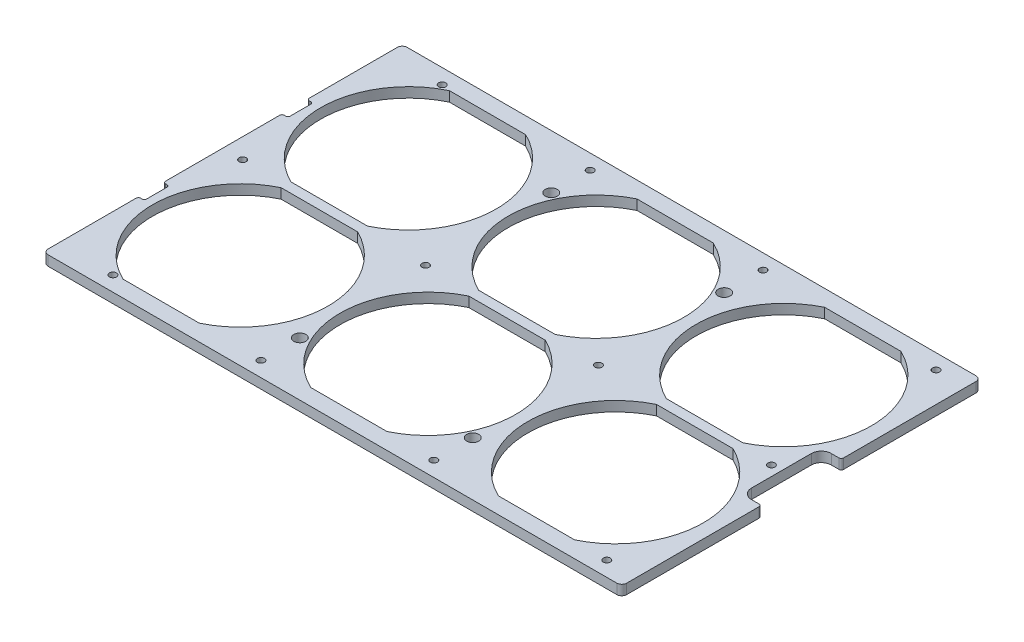
SolidWorks part; units mm, degrees
material "NEOPRENE"
ref_plane "Front" through (0, 0, 0) normal (0, 0, 1) x (1, 0, 0)
ref_plane "Top" through (0, 0, 0) normal (0, 1, 0) x (1, 0, 0)
ref_plane "Right" through (0, 0, 0) normal (1, 0, 0) x (0, 0, -1)
sketch "Sketch1" plane through (0, 0, 0) normal (0, 1, 0) x (1, 0, 0)
  line L0 (-24.3078, -3.1623) -> (24.3078, -3.1623)
  line L1 (-180.975, 114.3) -> (180.975, 114.3)
  line L2 (-184.15, 111.125) -> (-184.15, -111.125)
  line L3 (-180.975, -114.3) -> (180.975, -114.3)
  line L4 (184.15, 111.125) -> (184.15, -111.125)
  line L5 (-184.15, 114.3) -> (184.15, -114.3) construction
  line L6 (-184.15, -114.3) -> (184.15, 114.3) construction
  line L7 (95.1365, -3.1623) -> (143.7521, -3.1623)
  line L8 (95.1365, -3.1623) -> (95.1365, -103.8733) construction
  line L9 (95.1365, -103.8733) -> (143.7521, -103.8733)
  line L10 (143.7521, -3.1623) -> (143.7521, -103.8733) construction
  line L11 (95.1365, -3.1623) -> (143.7521, -103.8733) construction
  line L12 (95.1365, -103.8733) -> (143.7521, -3.1623) construction
  line L13 (-24.3078, -103.8733) -> (24.3078, -103.8733)
  line L14 (-143.7521, -3.1623) -> (-95.1365, -3.1623)
  line L15 (-143.7521, -103.8733) -> (-95.1365, -103.8733)
  line L16 (-24.3078, 103.8733) -> (24.3078, 103.8733)
  line L17 (-24.3078, 3.1623) -> (24.3078, 3.1623)
  line L18 (-143.7521, 103.8733) -> (-95.1365, 103.8733)
  line L19 (-143.7521, 3.1623) -> (-95.1365, 3.1623)
  line L20 (95.1365, 103.8733) -> (143.7521, 103.8733)
  line L21 (95.1365, 3.1623) -> (143.7521, 3.1623)
  line L22 (-95.1365, -103.8733) -> (-24.3078, -103.8733) construction
  line L23 (24.3078, -103.8733) -> (95.1365, -103.8733) construction
  line L24 (119.5086, 53.5178) -> (119.5086, -53.5178) construction
  line L25 (24.3078, 3.1623) -> (24.3078, -3.1623) construction
  line L26 (-175.3235, -53.5178) -> (-184.15, -53.5178) construction
  line L27 (175.3235, -53.5178) -> (184.15, -53.5178) construction
  line L28 (-24.3078, -103.8733) -> (-24.3078, -114.3) construction
  line L29 (-24.3078, 103.8733) -> (-24.3078, 114.3) construction
  arc A0 (95.1365, -3.1623) -> (95.1365, -103.8733) centre (119.5086, -53.5178) ccw
  arc A1 (143.7521, -3.1623) -> (143.7521, -103.8733) centre (119.38, -53.5178) cw
  arc A2 (-184.15, -111.125) -> (-180.975, -114.3) centre (-180.975, -111.125) ccw
  arc A3 (184.15, -111.125) -> (180.975, -114.3) centre (180.975, -111.125) cw
  arc A4 (184.15, 111.125) -> (180.975, 114.3) centre (180.975, 111.125) ccw
  arc A5 (-180.975, 114.3) -> (-184.15, 111.125) centre (-180.975, 111.125) ccw
  circle A6 centre (-149.225, -104.775) radius 2.2479 construction
  circle A8 centre (-55.0333, -104.775) radius 2.2479 construction
  arc A10 (-24.3078, -3.1623) -> (-24.3078, -103.8733) centre (0.0643, -53.5178) ccw
  arc A11 (24.3078, -3.1623) -> (24.3078, -103.8733) centre (-0.0643, -53.5178) cw
  arc A12 (-143.7521, -3.1623) -> (-143.7521, -103.8733) centre (-119.38, -53.5178) ccw
  arc A13 (-95.1365, -3.1623) -> (-95.1365, -103.8733) centre (-119.5086, -53.5178) cw
  arc A14 (-24.3078, 103.8733) -> (-24.3078, 3.1623) centre (0.0643, 53.5178) ccw
  arc A15 (24.3078, 103.8733) -> (24.3078, 3.1623) centre (-0.0643, 53.5178) cw
  arc A16 (-143.7521, 103.8733) -> (-143.7521, 3.1623) centre (-119.38, 53.5178) ccw
  arc A17 (-95.1365, 103.8733) -> (-95.1365, 3.1623) centre (-119.5086, 53.5178) cw
  arc A18 (95.1365, 103.8733) -> (95.1365, 3.1623) centre (119.5086, 53.5178) ccw
  arc A19 (143.7521, 103.8733) -> (143.7521, 3.1623) centre (119.38, 53.5178) cw
  circle A20 centre (55.0333, -104.775) radius 2.2479 construction
  circle A21 centre (165.1, -104.775) radius 2.2479 construction
  circle A22 centre (165.1, 104.775) radius 2.2479 construction
  circle A23 centre (55.0333, 104.775) radius 2.2479 construction
  circle A24 centre (-55.0333, 104.775) radius 2.2479 construction
  circle A25 centre (-149.225, 104.775) radius 2.2479 construction
  circle A26 centre (-149.225, -104.775) radius 2.2479
  circle A27 centre (-55.0333, -104.775) radius 2.2479
  circle A28 centre (55.0333, -104.775) radius 2.2479
  circle A29 centre (165.1, -104.775) radius 2.2479
  circle A30 centre (165.1, 104.775) radius 2.2479
  circle A31 centre (55.0333, 104.775) radius 2.2479
  circle A32 centre (-55.0333, 104.775) radius 2.2479
  circle A33 centre (-149.225, 104.775) radius 2.2479
  circle A34 centre (55.0291, 80.01) radius 2.2479 construction
  circle A35 centre (-55.0291, 80.01) radius 2.2479 construction
  circle A36 centre (-55.0333, 0) radius 2.2479 construction
  circle A37 centre (55.0333, 0) radius 2.2479 construction
  circle A38 centre (55.0291, -80.01) radius 2.2479 construction
  circle A39 centre (-55.0291, -80.01) radius 2.2479 construction
  circle A40 centre (55.0291, 80.01) radius 2.2479 construction
  circle A41 centre (-55.0291, 80.01) radius 2.2479 construction
  circle A42 centre (-55.0333, 0) radius 2.2479
  circle A43 centre (55.0333, 0) radius 2.2479
  circle A44 centre (55.0291, -80.01) radius 2.2479 construction
  circle A45 centre (-55.0291, -80.01) radius 2.2479 construction
  circle A46 centre (-55.0291, 80.01) radius 3.81
  circle A47 centre (-55.0291, -80.01) radius 3.81
  circle A48 centre (55.0291, -80.01) radius 3.81
  circle A49 centre (55.0291, 80.01) radius 3.81
  circle A50 centre (165.1, 0) radius 2.2479 construction
  circle A51 centre (165.1, 0) radius 2.2479
  circle A52 centre (-171.45, 0) radius 2.2479 construction
  circle A53 centre (-171.45, 0) radius 2.2479
  point P0 (0, 0)
  point P6 (119.4443, -53.5178)
  dimension "D4" = 111.887
  dimension "D8" = 3.175
  dimension "D9" = 7.62
  dimension "D1" = 368.3
  dimension "D2" = 228.6
  dimension "D3" = 100.711
  dimension "D5" = 48.6156
  dimension "D6" = 119.38
  dimension "D7" = 107.0356
  dimension "D11" = 3
  dimension "D12" = 2
extrude "Boss-Extrude1" add sketch "Sketch1" along normal blind 6.35
sketch "Sketch2" plane through (0, 6.35, 0) normal (0, 1, 0) x (1, 0, 0)
  line L0 (0, 0) -> (184.15, 0) construction
  line L1 (184.15, -111.125) -> (184.15, 111.125) construction
  line L2 (184.15, -111.125) -> (184.15, 111.125) construction
  line L3 (184.15, 25.4) -> (177.8, 25.4)
  line L4 (184.15, 25.4) -> (184.15, -25.4)
  line L5 (184.15, -25.4) -> (177.8, -25.4)
  line L6 (171.45, 19.05) -> (171.45, -19.05)
  arc A0 (177.8, -25.4) -> (171.45, -19.05) centre (177.8, -19.05) cw
  arc A1 (177.8, 25.4) -> (171.45, 19.05) centre (177.8, 19.05) ccw
  point P14 (171.45, -25.4)
  point P17 (171.45, 25.4)
  dimension "D3" = 6.35
  dimension "D1" = 12.7
  dimension "D2" = 50.8
extrude "Cut-Extrude1" cut sketch "Sketch2" against normal through all and the other way through all
sketch "Sketch3" plane through (0, 6.35, 0) normal (0, 1, 0) x (1, 0, 0)
  line L0 (-184.15, 111.125) -> (-184.15, -111.125) construction
  line L1 (-184.15, 53.6575) -> (-180.34, 53.6575)
  line L2 (-184.15, 53.6575) -> (-184.15, 37.7825)
  line L3 (-184.15, 37.7825) -> (-180.34, 37.7825)
  line L4 (-180.34, 53.6575) -> (-180.34, 37.7825)
  line L5 (-180.34, 45.72) -> (-184.15, 45.72) construction
  line L6 (0, 0) -> (-184.15, 0) construction
  line L8 (-184.15, -37.7825) -> (-180.34, -37.7825)
  line L9 (-180.34, -53.6575) -> (-180.34, -37.7825)
  line L10 (-184.15, -53.6575) -> (-180.34, -53.6575)
  line L11 (-184.15, -53.6575) -> (-184.15, -37.7825)
  dimension "D1" = 3.81
  dimension "D2" = 15.875
  dimension "D3" = 45.72
extrude "Cut-Extrude2" cut sketch "Sketch3" against normal through all
fillet "Fillet1" radius 1.524 10 edges at (184.15, 3.175, 25.4) (184.15, 3.175, -25.4) (-180.34, 3.175, 37.7825) (-184.15, 3.175, 37.7825) (-184.15, 3.175, 53.6575) (-180.34, 3.175, 53.6575) (-184.15, 3.175, -37.7825) (-180.34, 3.175, -37.7825) (-184.15, 3.175, -53.6575) (-180.34, 3.175, -53.6575)
